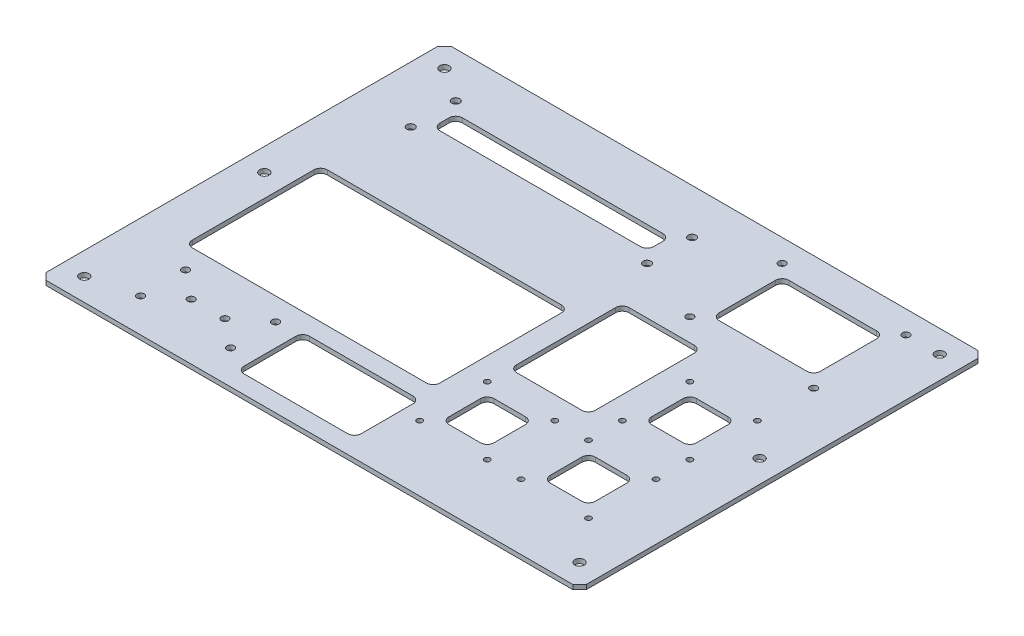
SolidWorks part; units mm, degrees
material "A-玻璃纤维"
ref_plane "前视基准面" through (0, 0, 0) normal (0, 0, 1) x (1, 0, 0)
ref_plane "上视基准面" through (0, 0, 0) normal (0, 1, 0) x (1, 0, 0)
ref_plane "右视基准面" through (0, 0, 0) normal (1, 0, 0) x (0, 0, -1)
sketch "草图1" plane through (0, 0, 0) normal (0, 1, 0) x (1, 0, 0)
  line L1 (-120, 90) -> (120, 90)
  line L2 (-120, 90) -> (-120, -90)
  line L3 (-120, -90) -> (120, -90)
  line L4 (120, 90) -> (120, -90)
  line L5 (0, -90) -> (0, 90) construction
  line L6 (-120, 0) -> (120, 0) construction
  point P56 (0, 0)
  dimension "D1" = 240
  dimension "D2" = 180
extrude "凸台-拉伸1" add sketch "草图1" along normal blind 2 contours L4 L1 L2 L3 region at (0, 0, 0)
sketch "草图3" plane through (0, 2, 0) normal (0, 1, 0) x (1, 0, 0)
  line L0 (0, 111.6719) -> (0, 0) construction
  line L1 (0, 0) -> (-162.8356, 0) construction
  line L2 (-120, 90) -> (-120, -90) construction
  circle A0 centre (-110, 80) radius 2.1
  circle A1 centre (-110, 0) radius 2.1
  circle A2 centre (-110, -80) radius 2.1
  circle A3 centre (110, -80) radius 2.1
  circle A4 centre (110, 0) radius 2.1
  circle A5 centre (110, 80) radius 2.1
  dimension "D1" = 10
  dimension "D2" = 160
  dimension "D3" = 4.2
  dimension "D4" = 4.2
  dimension "D5" = 10
extrude "切除-拉伸2" cut sketch "草图3" against normal blind 10
sketch "草图4" plane through (0, 2, 0) normal (0, 1, 0) x (1, 0, 0)
  line L0 (-120, 90) -> (120, 90) construction
  line L4 (40, 80) -> (95, 80) construction
  line L5 (40, 80) -> (40, 39) construction
  line L6 (40, 39) -> (95, 39) construction
  line L7 (95, 80) -> (95, 39) construction
  line L8 (67.5, 39) -> (67.5, 80) construction
  line L9 (40, 59.5) -> (95, 59.5) construction
  line L10 (65, -31) -> (95, -31) construction
  line L11 (65, 14) -> (95, 14) construction
  line L12 (65, 14) -> (65, -16) construction
  line L13 (65, -16) -> (95, -16) construction
  line L14 (95, 14) -> (95, -16) construction
  line L15 (80, -16) -> (80, 14) construction
  line L16 (65, -1) -> (95, -1) construction
  line L17 (65, -31) -> (65, -61) construction
  line L18 (65, -61) -> (95, -61) construction
  line L19 (95, -31) -> (95, -61) construction
  line L20 (80, -61) -> (80, -31) construction
  line L21 (65, -46) -> (95, -46) construction
  line L22 (20, -31) -> (50, -31) construction
  line L23 (20, -31) -> (20, -61) construction
  line L24 (20, -61) -> (50, -61) construction
  line L25 (50, -31) -> (50, -61) construction
  line L26 (35, -61) -> (35, -31) construction
  line L27 (20, -46) -> (50, -46) construction
  circle A1 centre (-110, 80) radius 2.1 construction
  circle A2 centre (110, 80) radius 2.1 construction
  circle A4 centre (40, 80) radius 1.6
  circle A5 centre (95, 80) radius 1.6
  circle A6 centre (40, 39) radius 1.6
  circle A7 centre (95, 39) radius 1.6
  circle A8 centre (110, 0) radius 2.1 construction
  circle A9 centre (65, 14) radius 1.25
  circle A10 centre (95, 14) radius 1.25
  circle A11 centre (95, -16) radius 1.25
  circle A12 centre (65, -16) radius 1.25
  circle A13 centre (95, -31) radius 1.25
  circle A14 centre (65, -31) radius 1.25
  circle A15 centre (65, -61) radius 1.25
  circle A16 centre (95, -61) radius 1.25
  circle A17 centre (50, -31) radius 1.25
  circle A18 centre (20, -31) radius 1.25
  circle A19 centre (20, -61) radius 1.25
  circle A20 centre (50, -61) radius 1.25
  point P33 (80, -46)
  point P42 (35, -46)
  point P60 (80, -1)
  point P84 (67.5, 59.5)
  line B0 (-42.5, 40) -> (-42.5, 102.5257) construction
  circle B1 centre (-95, 50) radius 1.75
  circle B2 centre (-95, 70) radius 1.75
  circle B3 centre (10, 70) radius 1.75
  circle B4 centre (10, 50) radius 1.75
  dimension "D7" = 3.2
  dimension "D18" = 2.5
  dimension "D1" = 15
  dimension "D2" = 20
  dimension "D3" = 55
  dimension "D4" = 41
  dimension "D5" = 15
  dimension "D6" = 10
  dimension "D8" = 30
  dimension "D9" = 30
  dimension "D10" = 25
  dimension "D11" = 15
  dimension "D12" = 15
  dimension "D13" = 30
  dimension "D14" = 30
  dimension "D15" = 30
  dimension "D16" = 30
  dimension "D17" = 15
sketch_block_instance "块-电池安装孔-3"
sketch_block "块-电池安装孔" parameters "D2"=3.5, "D1"=20
extrude "切除-拉伸3" cut sketch "草图4" against normal blind 10 and the other way through all contours B2 | B3 | B4 | B1 | A4 | A5 | A7 | A6 | A9 | A10 | A11 | A12 | A14 | A16 | A15 | A19 | A20 | A18 | A17 | A13 region at (40, 2, -80) region at (95, 2, -80) region at (40, 2, -39) region at (95, 2, -39) region at (65, 2, -14) region at (95, 2, -14) region at (95, 2, 16) region at (65, 2, 16) region at (65, 2, 31) region at (65, 2, 61) region at (95, 2, 61) region at (50, 2, 31) region at (20, 2, 31) region at (20, 2, 61) region at (50, 2, 61) region at (-95, 2, -50) region at (-95, 2, -70) region at (10, 2, -70) region at (10, 2, -50)
sketch "草图5" plane through (0, 2, 0) normal (0, 1, 0) x (1, 0, 0)
  line L0 (-70, -90) -> (-70, -2.7152) construction
  line L1 (-120, -90) -> (120, -90) construction
  line L2 (-110, -65) -> (-36.5298, -65) construction
  circle A0 centre (-110, -80) radius 2.1 construction
  circle A1 centre (-62.5, -65) radius 1.6
  circle A2 centre (-77.5, -65) radius 1.6
  circle A3 centre (-50, -75) radius 1.6
  circle A4 centre (-90, -75) radius 1.6
  circle A5 centre (-90, -55) radius 1.6
  circle A6 centre (-50, -55) radius 1.6
  dimension "D2" = 15
  dimension "D3" = 3.2
  dimension "D5" = 3.2
  dimension "D6" = 40
  dimension "D7" = 20
  dimension "D1" = 40
  dimension "D4" = 25
extrude "切除-拉伸4" cut sketch "草图5" against normal blind 10
sketch "草图6" plane through (0, 2, 0) normal (0, 1, 0) x (1, 0, 0)
  line L0 (45, 75) -> (90, 75)
  line L1 (-100, 15) -> (10, 15)
  line L2 (-100, 15) -> (-100, -45)
  line L3 (-100, -45) -> (10, -45)
  line L4 (10, 15) -> (10, -45)
  line L5 (-45, -45) -> (-45, 15) construction
  line L6 (-100, -15) -> (10, -15) construction
  line L11 (40, 80) -> (95, 80) construction
  line L12 (40, 80) -> (40, 39) construction
  line L13 (40, 39) -> (95, 39) construction
  line L14 (95, 80) -> (95, 39) construction
  line L15 (67.5, 39) -> (67.5, 80) construction
  line L16 (40, 59.5) -> (95, 59.5) construction
  line L17 (90, 75) -> (90, 44)
  line L18 (45, 44) -> (90, 44)
  line L19 (45, 75) -> (45, 44)
  line L20 (70, -11) -> (90, -11)
  line L21 (65, 14) -> (95, 14)
  line L22 (65, 14) -> (65, -16)
  line L23 (65, -16) -> (95, -16)
  line L24 (95, 14) -> (95, -16)
  line L25 (80, -16) -> (80, 14) construction
  line L26 (65, -1) -> (95, -1) construction
  line L27 (65, -31) -> (95, -31)
  line L28 (65, -31) -> (65, -61)
  line L29 (65, -61) -> (95, -61)
  line L30 (95, -31) -> (95, -61)
  line L31 (80, -61) -> (80, -31) construction
  line L32 (65, -46) -> (95, -46) construction
  line L33 (20, -31) -> (50, -31)
  line L34 (20, -31) -> (20, -61)
  line L35 (20, -61) -> (50, -61)
  line L36 (50, -31) -> (50, -61)
  line L37 (35, -61) -> (35, -31) construction
  line L38 (20, -46) -> (50, -46) construction
  line L39 (90, 9) -> (90, -11)
  line L40 (70, 9) -> (90, 9)
  line L41 (70, 9) -> (70, -11)
  line L42 (70, -36) -> (90, -36)
  line L43 (90, -36) -> (90, -56)
  line L44 (70, -56) -> (90, -56)
  line L45 (70, -36) -> (70, -56)
  line L46 (25, -36) -> (25, -56)
  line L47 (25, -56) -> (45, -56)
  line L48 (45, -36) -> (45, -56)
  line L49 (25, -36) -> (45, -36)
  line L51 (20, 29) -> (55, 29)
  line L52 (20, 29) -> (20, -21)
  line L53 (20, -21) -> (55, -21)
  line L54 (55, 29) -> (55, -21)
  line L55 (37.5, -21) -> (37.5, 29) construction
  line L56 (20, 4) -> (55, 4) construction
  line L57 (-95, 70) -> (10, 70)
  line L58 (-95, 70) -> (-95, 50)
  line L59 (-95, 50) -> (10, 50)
  line L60 (10, 70) -> (10, 50)
  line L61 (-42.5, 50) -> (-42.5, 70) construction
  line L62 (-95, 60) -> (10, 60) construction
  line L64 (-90, 65) -> (-90, 55)
  line L65 (-90, 55) -> (5, 55)
  line L66 (5, 65) -> (5, 55)
  line L67 (-90, 65) -> (5, 65)
  circle A0 centre (10, 50) radius 1.75 construction
  circle A1 centre (-110, 0) radius 2.1 construction
  circle A2 centre (-90, -55) radius 1.6 construction
  circle A3 centre (20, -31) radius 1.25 construction
  circle A4 centre (40, 39) radius 1.6 construction
  circle A5 centre (65, 14) radius 1.25 construction
  circle A6 centre (50, -31) radius 1.25 construction
  point P140 (80, -1)
  point P157 (37.5, 4)
  point P173 (80, -46)
  point P219 (35, -46)
  point P232 (-45, -15)
  point P289 (-42.5, 60)
  point P361 (67.5, 59.5)
  dimension "D3" = 10
  dimension "D1" = 35
  dimension "D2" = 10
  dimension "D4" = 10
  dimension "D5" = 5
  dimension "D6" = 5
  dimension "D7" = 10
  dimension "D8" = 10
  dimension "D9" = 10
  dimension "D10" = 10
  dimension "D11" = 5
extrude "切除-拉伸5" cut sketch "草图6" against normal blind 10 contours L4 L1 L2 L3 | L54 L51 L52 L53 | L40 L41 L20 L39 | L42 L45 L44 L43 | L49 L46 L47 L48 | L0 L19 L18 L17 | L67 L64 L65 L66 region at (67.5, 2, -59.5) region at (-45, 2, 15) region at (80, 2, 1) region at (80, 2, 46) region at (35, 2, 46) region at (37.5, 2, -4) region at (-42.5, 2, -60)
sketch "草图7" plane through (0, 2, 0) normal (0, 1, 0) x (1, 0, 0)
  line L0 (-120, -90) -> (120, -90) construction
  line L1 (-40, -53) -> (12, -53)
  line L2 (-40, -53) -> (-40, -82)
  line L3 (-40, -82) -> (12, -82)
  line L4 (12, -53) -> (12, -82)
  line L5 (-14, -82) -> (-14, -53) construction
  line L6 (-40, -67.5) -> (12, -67.5) construction
  line L7 (-100, -45) -> (10, -45) construction
  circle A0 centre (-50, -75) radius 1.6 construction
  circle A1 centre (20, -61) radius 1.25 construction
  point P116 (-14, -67.5)
  dimension "D1" = 8
  dimension "D2" = 10
  dimension "D3" = 8
  dimension "D4" = 8
extrude "切除-拉伸6" cut sketch "草图7" against normal blind 10
fillet "圆角1" radius 3 32 edges at (10, 1, 45) (-100, 1, 45) (10, 1, -15) (90, 1, -9) (90, 1, 11) (70, 1, 11) (70, 1, -9) (45, 1, 36) (45, 1, 56) (25, 1, 56) (25, 1, 36) (90, 1, -75) (90, 1, -44) (45, 1, -44) (45, 1, -75) (90, 1, 36) (90, 1, 56) (70, 1, 56) (70, 1, 36) (55, 1, 21) (20, 1, 21) (20, 1, -29) (55, 1, -29) (-100, 1, -15) (5, 1, -65) (5, 1, -55) (-90, 1, -55) (-90, 1, -65) (12, 1, 53) (12, 1, 82) (-40, 1, 82) (-40, 1, 53)
chamfer "倒角1" distance 3 angle 45 4 edges at (-120, 1, 90) (120, 1, 90) (120, 1, -90) (-120, 1, -90)
